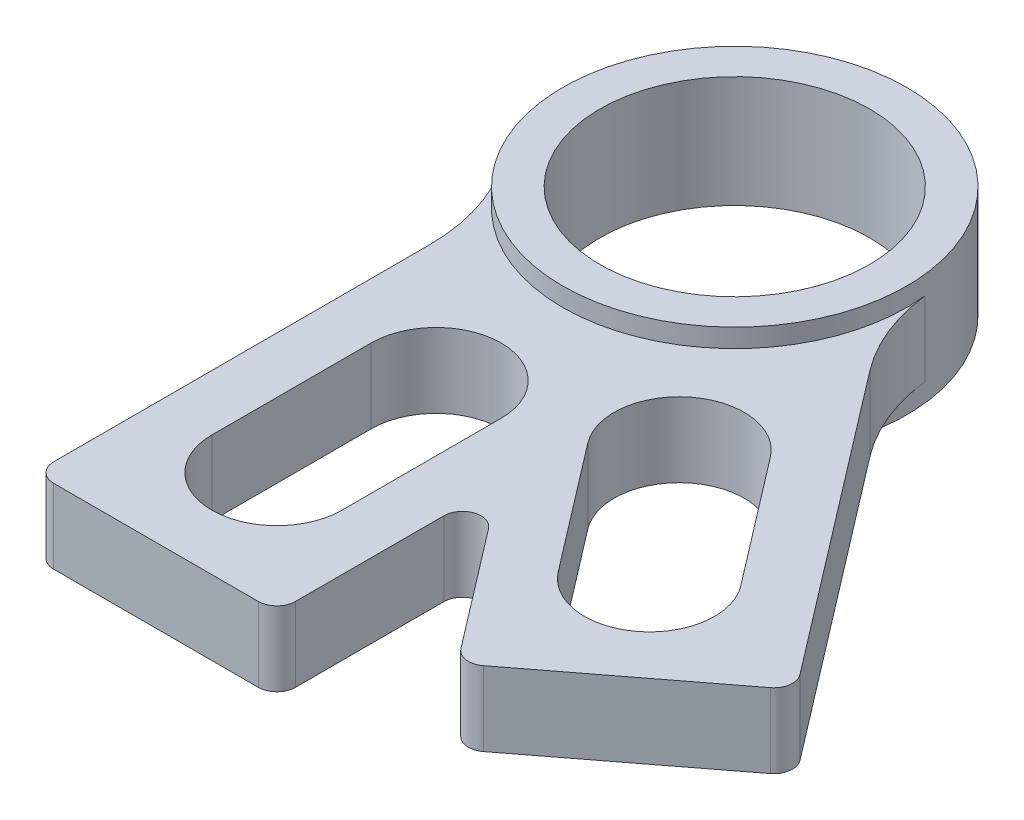
SolidWorks part; units mm, degrees
material "AISI 4130 Steel, annealed at 865C"
ref_plane "Front Plane" through (0, 0, 0) normal (0, 0, 1) x (1, 0, 0)
ref_plane "Top Plane" through (0, 0, 0) normal (0, 1, 0) x (1, 0, 0)
ref_plane "Right Plane" through (0, 0, 0) normal (1, 0, 0) x (0, 0, -1)
sketch "Sketch1" plane through (0, 0, 0) normal (0, 1, 0) x (1, 0, 0)
  line L0 (0, 0) -> (0, -49.3903) construction
  line L1 (0, 0) -> (30.021, -39.2192) construction
  line L2 (0, -39.0716) -> (0, -25.4826) construction
  line L3 (-5.5562, -39.0716) -> (-5.5562, -25.4826)
  line L4 (5.5563, -39.0716) -> (5.5563, -25.4826)
  line L5 (23.7489, -31.0254) -> (15.4891, -20.2348) construction
  line L6 (19.3369, -34.4027) -> (11.0771, -23.6121)
  line L7 (28.1609, -27.6481) -> (19.9011, -16.8576)
  line L8 (0, -49.3903) -> (0, -44.6278) construction
  line L9 (30.021, -39.2192) -> (27.1262, -35.4374) construction
  line L10 (-10.3187, -49.3903) -> (10.3188, -49.3903)
  line L11 (21.8272, -45.4912) -> (38.2147, -32.9471)
  line L12 (-10.3187, -49.3903) -> (-10.3187, -10.4432)
  line L13 (10.3188, -49.3903) -> (10.3188, -30.4567)
  line L14 (38.2147, -32.9471) -> (14.5415, -2.0206)
  line L15 (21.8272, -45.4912) -> (10.3188, -30.4567)
  line L16 (173.0607, -226.0852) -> (14.2404, -18.6035) construction
  line L22 (0, 0) -> (10.3188, -30.4567) construction
  circle A0 centre (0, 0) radius 11.5062
  circle A1 centre (0, 0) radius 14.6812
  arc A2 (-5.5562, -39.0716) -> (5.5563, -39.0716) centre (0, -39.0716) ccw
  arc A3 (5.5563, -25.4826) -> (-5.5562, -25.4826) centre (0, -25.4826) ccw
  arc A4 (19.3369, -34.4027) -> (28.1609, -27.6481) centre (23.7489, -31.0254) ccw
  arc A5 (19.9011, -16.8576) -> (11.0771, -23.6121) centre (15.4891, -20.2348) ccw
  point P8 (0, -32.2771)
  point P13 (19.619, -25.6301)
  point P25 (0, -49.3903)
  point P27 (30.021, -39.2192)
  dimension "D2" = 29.3624
  dimension "D3" = 4.7625
  dimension "D4" = 4.7625
  dimension "D5" = 13.589
  dimension "D6" = 49.3903
  dimension "D7" = 20.6375
extrude "Bearing_Insert_Extrude" add sketch "Sketch1" along normal mid plane 9.525 contours A1 A0 region at (-5.4988, 0, -13.1636)
extrude "Apex_Slot_Insert_Extrude" add sketch "Sketch1<4>" along normal mid plane 6.35 contours A1 L12 L10 L13 L15 L11 L14 A5 L7 A4 L6 A3 L4 A2 L3 region at (9.7483, 0, 28.773)
sketch "Sketch1<4>" plane through (0, 0, 0) normal (0, 1, 0) x (1, 0, 0) same geometry as "Sketch1"
fillet "Fillet1" radius 16.002 2 edges at (14.5415, 0, 2.0206) (-10.3187, 0, 10.4432)
fillet "Fillet2" radius 1.5875 5 edges at (38.2147, 0, 32.9471) (21.8272, 0, 45.4912) (10.3188, 0, 30.4567) (10.3188, 0, 49.3903) (-10.3187, 0, 49.3903)
equation "\"Apex_thickness\"= .25"
equation "\"Bearing_diameter\"= 0.906in"
equation "\"A-arm_angle\"= 39.1893"
equation "\"D1@Sketch1\"=\"Bearing_diameter\""
equation "\"D1@Apex_Slot_Insert_Extrude\"=\"Apex_thickness\""
